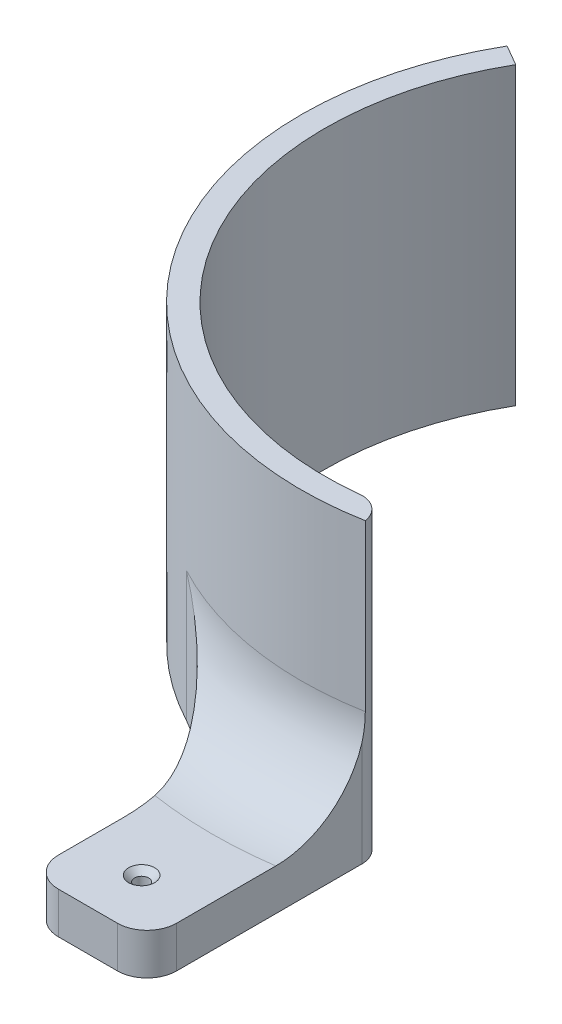
SolidWorks part; units mm, degrees
ref_plane "Piano frontale" through (0, 0, 0) normal (0, 0, 1) x (1, 0, 0)
ref_plane "Piano superiore" through (0, 0, 0) normal (0, 1, 0) x (1, 0, 0)
ref_plane "Piano destro" through (0, 0, 0) normal (1, 0, 0) x (0, 0, -1)
sketch "Schizzo1" plane through (0, 0, 0) normal (0, 1, 0) x (1, 0, 0)
  line L0 (-47.6314, 27.5) -> (-44.1673, 25.5)
  line L2 (0, 0) -> (-44.1673, 25.5) construction
  line L3 (0, 0) -> (44.1673, 25.5) construction
  line L4 (0, 0) -> (0, 51.9167) construction
  line L5 (-10, -54.0833) -> (-10, -86.0833)
  line L6 (-5, -91.0833) -> (5, -91.0833)
  line L7 (10, -86.0833) -> (10, -54.0833)
  line L8 (0, -91.0833) -> (0, 0) construction
  line L9 (10, -54.0833) -> (10, -50.01)
  arc A0 (-47.6314, 27.5) -> (10, -54.0833) centre (0, 0) ccw
  arc A1 (-44.1673, 25.5) -> (10, -50.01) centre (0, 0) ccw
  arc A3 (10, -86.0833) -> (5, -91.0833) centre (5, -86.0833) cw
  arc A4 (-5, -91.0833) -> (-10, -86.0833) centre (-5, -86.0833) cw
  point P14 (10, -91.0833)
  point P17 (-10, -91.0833)
  dimension "D1" = 110
  dimension "D2" = 4
  dimension "D5" = 20
  dimension "D7" = 5
  dimension "D3" = 120
  dimension "D4" = 60
  dimension "D6" = 37
extrude "Estrusione-Estrusione1" add sketch "Schizzo1" along normal blind 50 contours A0 L0 A1 L9
ref_plane "Piano1" through (0, 0, -27.5) normal (0, 0, 1) x (1, 0, 0)
extrude "Estrusione-Estrusione2" add sketch "Schizzo1<3>" along normal blind 7 contours A0 L5 L6 L7 region at (0, 0, 72.6328)
sketch "Schizzo1<3>" plane through (0, 0, 0) normal (0, 1, 0) x (1, 0, 0) same geometry as "Schizzo1"
sketch "Schizzo2" plane through (0, 7, 0) normal (0, -1, 0) x (1, 0, 0)
  line L1 (0, 82) -> (0, 0) construction
  point P0 (0, 82)
  point P14 (0, 82)
  dimension "D1" = 82
hole_wizard "Foro svasato per Vite M2-1" positions "Schizzo2" profile "Schizzo4" countersink size "M2" standard "ISO"
sketch "Schizzo4" plane through (0, 7, 82) normal (1, 0, 0) x (0, 0, 1)
  line L0 (0, 0) -> (0, 12.661)
  line L1 (0, 12.661) -> (1.2, 11.94)
  line L2 (1.2, 11.94) -> (1.2, 1)
  line L3 (1.2, 1) -> (2.2, 0)
  line L5 (2.2, 0) -> (0, 0)
  line L6 (-1.2, 1) -> (-2.2, 0) construction
  line L10 (0, 12.661) -> (-1.2, 11.94) construction
  line L11 (0, -6.35) -> (0, 107.95) construction
  dimension "Hole Dia." = 2.4
  dimension "Hole Depth" = 11.94
  dimension "Near C'Sink Dia." = 4.4
  dimension "Near C'Sink Angle" = 90
  dimension "Drill Angle" = 118
fillet "Raccordo1" radius 30 1 edges at (-10, 3.5, 54.0833)
fillet "Raccordo2" radius 15 1 edges at (-8.4127, 7, 54.3528)
fillet "Raccordo3" radius 4 1 edges at (10, 25, 50.01)
